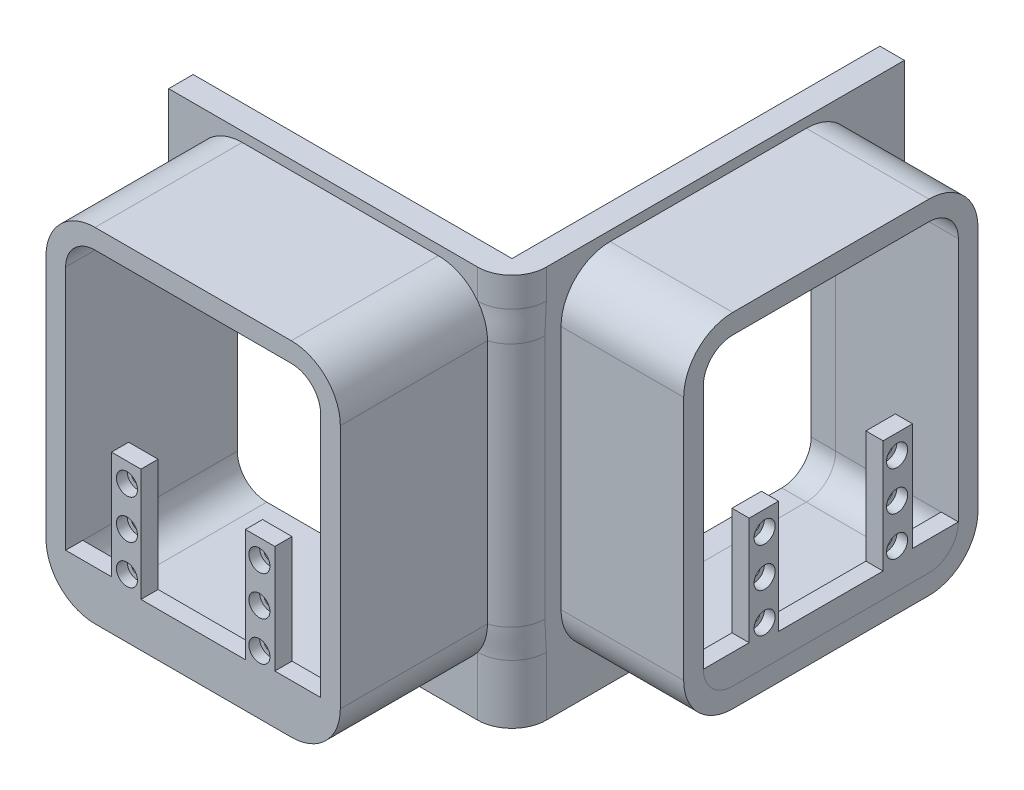
SolidWorks part; units mm, degrees
ref_plane "Front Plane" through (0, 0, 0) normal (0, 0, 1) x (1, 0, 0)
ref_plane "Top Plane" through (0, 0, 0) normal (0, 1, 0) x (1, 0, 0)
ref_plane "Right Plane" through (0, 0, 0) normal (1, 0, 0) x (0, 0, -1)
sketch "Sketch1" plane through (0, 0, 0) normal (0, 0, 1) x (1, 0, 0)
  line L1 (-20, -35) -> (20, -35)
  line L2 (-30, -25) -> (-30, 25)
  line L3 (-20, 35) -> (20, 35)
  line L4 (30, -25) -> (30, 25)
  line L5 (-30, -35) -> (30, 35) construction
  line L6 (-30, 35) -> (30, -35) construction
  arc A1 (20, 35) -> (30, 25) centre (20, 25) cw
  arc A2 (20, -35) -> (30, -25) centre (20, -25) ccw
  arc A3 (-20, -35) -> (-30, -25) centre (-20, -25) cw
  arc A4 (-30, 25) -> (-20, 35) centre (-20, 25) cw
  point P0 (0, 0)
  dimension "D1" = 60
  dimension "D3" = 10
  dimension "D2" = 70
extrude "Boss-Extrude1" add sketch "Sketch1" against normal blind 30
ref_plane "Plane1" through (60, 0, 0) normal (1, 0, 0) x (0, 0, -1)
ref_plane "Plane2" through (60, 0, 0) normal (1, 0, 0) x (0, 0, -1)
sketch "Sketch10" plane through (0, 0, -30) normal (0, 0, -1) x (-1, 0, 0)
  line L0 (0, -3) -> (0, 0) construction
  line L1 (-35, -43) -> (35, -43)
  line L2 (-35, -43) -> (-35, 37)
  line L3 (-35, 37) -> (35, 37)
  line L4 (35, -43) -> (35, 37)
  line L5 (-35, -43) -> (35, 37) construction
  line L6 (-35, 37) -> (35, -43) construction
  point P0 (0, -3)
  dimension "D3" = 3
  dimension "D1" = 80
  dimension "D2" = 70
extrude "Boss-Extrude6" add sketch "Sketch10" along normal blind 80
sketch "Sketch2" plane through (60, 0, 0) normal (1, 0, 0) x (0, 0, -1)
  line L2 (0, 0) -> (146.6861, 0) construction
  line L3 (70, 0) -> (70, 30) construction
  line L5 (30, 37) -> (30, -43) construction
  line L6 (110, 37) -> (110, -43) construction
  line L7 (50, -35) -> (90, -35)
  line L8 (40, -25) -> (40, 25)
  line L9 (50, 35) -> (90, 35)
  line L10 (100, -25) -> (100, 25)
  line L11 (40, -35) -> (100, 35) construction
  line L12 (40, 35) -> (100, -35) construction
  arc A1 (50, -35) -> (40, -25) centre (50, -25) cw
  arc A2 (90, -35) -> (100, -25) centre (90, -25) ccw
  arc A3 (90, 35) -> (100, 25) centre (90, 25) cw
  arc A4 (40, 25) -> (50, 35) centre (50, 25) cw
  dimension "D1" = 60
  dimension "D3" = 10
  dimension "D2" = 70
extrude "Boss-Extrude2" add sketch "Sketch2" against normal up to surface (25 mm away) separate body up to face at (35, -3, -70)
sketch "Sketch11" plane through (0, 37, 0) normal (0, 1, 0) x (1, 0, 0)
  line L1 (-35, 110) -> (30, 110)
  line L2 (-35, 110) -> (-35, 35)
  line L3 (-35, 35) -> (30, 35)
  line L4 (30, 110) -> (30, 35)
  dimension "D1" = 75
  dimension "D2" = 65
extrude "Cut-Extrude5" cut sketch "Sketch11" against normal through all
sketch "Sketch4" plane through (35, 0, 0) normal (-1, 0, 0) x (0, 0, 1)
  line L8 (-90, -31) -> (-50, -31)
  line L9 (-96, 25) -> (-96, -25)
  line L10 (-50, 31) -> (-90, 31)
  line L11 (-44, -25) -> (-44, 25)
  line L12 (-90, -31) -> (-50, -31)
  line L13 (-96, 25) -> (-96, -25)
  line L14 (-50, 31) -> (-90, 31)
  line L15 (-44, -25) -> (-44, 25)
  arc A10 (-96, -25) -> (-90, -31) centre (-90, -25) ccw
  arc A11 (-90, 31) -> (-96, 25) centre (-90, 25) ccw
  arc A12 (-44, 25) -> (-50, 31) centre (-50, 25) ccw
  arc A13 (-50, -31) -> (-44, -25) centre (-50, -25) ccw
  arc A14 (-96, -25) -> (-90, -31) centre (-90, -25) ccw
  arc A15 (-90, 31) -> (-96, 25) centre (-90, 25) ccw
  arc A16 (-44, 25) -> (-50, 31) centre (-50, 25) ccw
  arc A17 (-50, -31) -> (-44, -25) centre (-50, -25) ccw
  dimension "D1" = 4
extrude "Cut-Extrude2" cut sketch "Sketch4" against normal through all contours L12 A17 L15 A16 L14 A15 L13 A14 region at (35, 0, -70)
sketch "Sketch5" plane through (60, 0, 0) normal (1, 0, 0) x (0, 0, -1)
  line L0 (70, 0) -> (70, -31) construction
  line L1 (53.35, -3) -> (59.35, -3)
  line L2 (59.35, -3) -> (59.35, -26)
  line L3 (59.35, -26) -> (80.65, -26)
  line L4 (80.65, -26) -> (80.65, -3)
  line L5 (80.65, -3) -> (86.65, -3)
  line L6 (86.65, -3) -> (86.65, -25)
  line L8 (53.35, -3) -> (53.35, -25)
  line L10 (70, 0) -> (83.5, 0) construction
  line L11 (83.5, 0) -> (83.5, -7) construction
  line L12 (83.5, -7) -> (83.5, -15) construction
  line L13 (83.5, -15) -> (83.5, -23) construction
  line L14 (90, -31) -> (50, -31) construction
  line L15 (50, -31) -> (90, -31)
  line L16 (53.35, -25) -> (44, -25)
  line L17 (86.65, -25) -> (96, -25)
  circle A0 centre (70, 0) radius 11 construction
  arc A1 (44, -25) -> (50, -31) centre (50, -25) ccw construction
  circle A2 centre (83.5, -7) radius 1.25
  arc A3 (44, -25) -> (50, -31) centre (50, -25) ccw
  circle A5 centre (83.5, -15) radius 1.25
  circle A6 centre (83.5, -23) radius 1.25
  circle A7 centre (56.5, -7) radius 1.25
  circle A8 centre (56.5, -15) radius 1.25
  circle A9 centre (56.5, -23) radius 1.25
  arc A10 (90, -31) -> (96, -25) centre (90, -25) ccw
  point P8 (70, -26)
  point P14 (70, -31)
  dimension "D1" = 22
  dimension "D6" = 2.5
  dimension "D3" = 21.3
  dimension "D4" = 13.5
  dimension "D5" = 7
  dimension "D7" = 8
  dimension "D8" = 8
  dimension "D9" = 6
  dimension "D10" = 5
  dimension "D12" = 3
extrude "Boss-Extrude3" add sketch "Sketch5" against normal blind 3.5
sketch "Sketch13" plane through (35, 0, 0) normal (1, 0, 0) x (0, 0, -1)
  line L4 (44, 25) -> (44, -25)
  line L5 (50, -31) -> (90, -31)
  line L6 (96, -25) -> (96, 25)
  line L7 (90, 31) -> (50, 31)
  line L8 (44, 25) -> (44, -25)
  line L9 (50, -31) -> (90, -31)
  line L10 (96, -25) -> (96, 25)
  line L11 (90, 31) -> (50, 31)
  arc A6 (50, 31) -> (44, 25) centre (50, 25) ccw
  arc A7 (44, -25) -> (50, -31) centre (50, -25) ccw
  arc A8 (90, -31) -> (96, -25) centre (90, -25) ccw
  arc A9 (96, 25) -> (90, 31) centre (90, 25) ccw
  arc A10 (50, 31) -> (44, 25) centre (50, 25) ccw
  arc A11 (44, -25) -> (50, -31) centre (50, -25) ccw
  arc A12 (90, -31) -> (96, -25) centre (90, -25) ccw
  arc A13 (96, 25) -> (90, 31) centre (90, 25) ccw
  dimension "D1" = 0
extrude "Cut-Extrude6" cut sketch "Sketch13" against normal up to surface (5 mm away) up to face at (30, -3, -72.5)
sketch "Sketch14" plane through (0, 0, 0) normal (0, 0, 1) x (1, 0, 0)
  line L8 (20, 31) -> (-20, 31)
  line L9 (26, -25) -> (26, 25)
  line L10 (-20, -31) -> (20, -31)
  line L11 (-26, 25) -> (-26, -25)
  line L12 (20, 31) -> (-20, 31)
  line L13 (26, -25) -> (26, 25)
  line L14 (-20, -31) -> (20, -31)
  line L15 (-26, 25) -> (-26, -25)
  arc A10 (26, 25) -> (20, 31) centre (20, 25) ccw
  arc A11 (20, -31) -> (26, -25) centre (20, -25) ccw
  arc A12 (-26, -25) -> (-20, -31) centre (-20, -25) ccw
  arc A13 (-20, 31) -> (-26, 25) centre (-20, 25) ccw
  arc A14 (26, 25) -> (20, 31) centre (20, 25) ccw
  arc A15 (20, -31) -> (26, -25) centre (20, -25) ccw
  arc A16 (-26, -25) -> (-20, -31) centre (-20, -25) ccw
  arc A17 (-20, 31) -> (-26, 25) centre (-20, 25) ccw
  dimension "D1" = 4
extrude "Cut-Extrude7" cut sketch "Sketch14" against normal up to surface (35 mm away) up to face at (-2.5, -3, -35)
sketch "Sketch15" plane through (0, 0, 0) normal (0, 0, 1) x (1, 0, 0)
  line L0 (0, 0) -> (0, -17.9719) construction
  line L1 (-16.65, -3) -> (-10.65, -3)
  line L2 (-10.65, -3) -> (-10.65, -26)
  line L3 (-10.65, -26) -> (10.65, -26)
  line L4 (10.65, -26) -> (10.65, -3)
  line L5 (10.65, -3) -> (16.65, -3)
  line L6 (16.65, -3) -> (16.65, -25)
  line L8 (-16.65, -3) -> (-16.65, -25)
  line L10 (0, 0) -> (13.5, 0) construction
  line L11 (13.5, 0) -> (13.5, -7) construction
  line L12 (13.5, -7) -> (13.5, -15) construction
  line L13 (13.5, -15) -> (13.5, -23) construction
  line L14 (-20, -31) -> (20, -31) construction
  line L15 (-20, -31) -> (20, -31)
  line L16 (26, -25) -> (16.65, -25)
  line L17 (-26, -25) -> (-16.65, -25)
  circle A0 centre (0, 0) radius 11 construction
  circle A1 centre (13.5, -7) radius 1.25
  circle A3 centre (13.5, -15) radius 1.25
  circle A4 centre (13.5, -23) radius 1.25
  circle A5 centre (-13.5, -7) radius 1.25
  circle A6 centre (-13.5, -15) radius 1.25
  circle A7 centre (-13.5, -23) radius 1.25
  arc A9 (-26, -25) -> (-20, -31) centre (-20, -25) ccw
  arc A10 (26, -25) -> (20, -31) centre (20, -25) cw
  point P5 (0, -26)
  dimension "D1" = 22
  dimension "D5" = 2.5
  dimension "D2" = 21.3
  dimension "D3" = 13.5
  dimension "D4" = 7
  dimension "D6" = 8
  dimension "D7" = 8
  dimension "D8" = 6
  dimension "D9" = 5
  dimension "D10" = 3
extrude "Boss-Extrude7" add sketch "Sketch15" against normal blind 3.5
sketch "Sketch16" plane through (60, 0, 0) normal (1, 0, 0) x (0, 0, -1)
  circle A0 centre (83.5, -7) radius 2.15
  circle A1 centre (83.5, -15) radius 2.15
  circle A2 centre (83.5, -23) radius 2.15
  circle A3 centre (56.5, -23) radius 2.15
  circle A4 centre (56.5, -15) radius 2.15
  circle A5 centre (56.5, -7) radius 2.15
  dimension "D1" = 4.3
extrude "Cut-Extrude8" cut sketch "Sketch16" against normal blind 2.2
fillet "Fillet1" radius 7 1 edges at (35, -3, -30)
fillet "Fillet2" [suppressed] radius 10
sketch "Sketch17" plane through (0, 0, 0) normal (0, 0, 1) x (1, 0, 0)
  circle A0 centre (-13.5, -7) radius 2.15
  circle A1 centre (-13.5, -15) radius 2.15
  circle A2 centre (-13.5, -23) radius 2.15
  circle A3 centre (13.5, -7) radius 2.15
  circle A4 centre (13.5, -15) radius 2.15
  circle A5 centre (13.5, -23) radius 2.15
  dimension "D1" = 4.3
extrude "Cut-Extrude9" cut sketch "Sketch17" against normal blind 2.2
